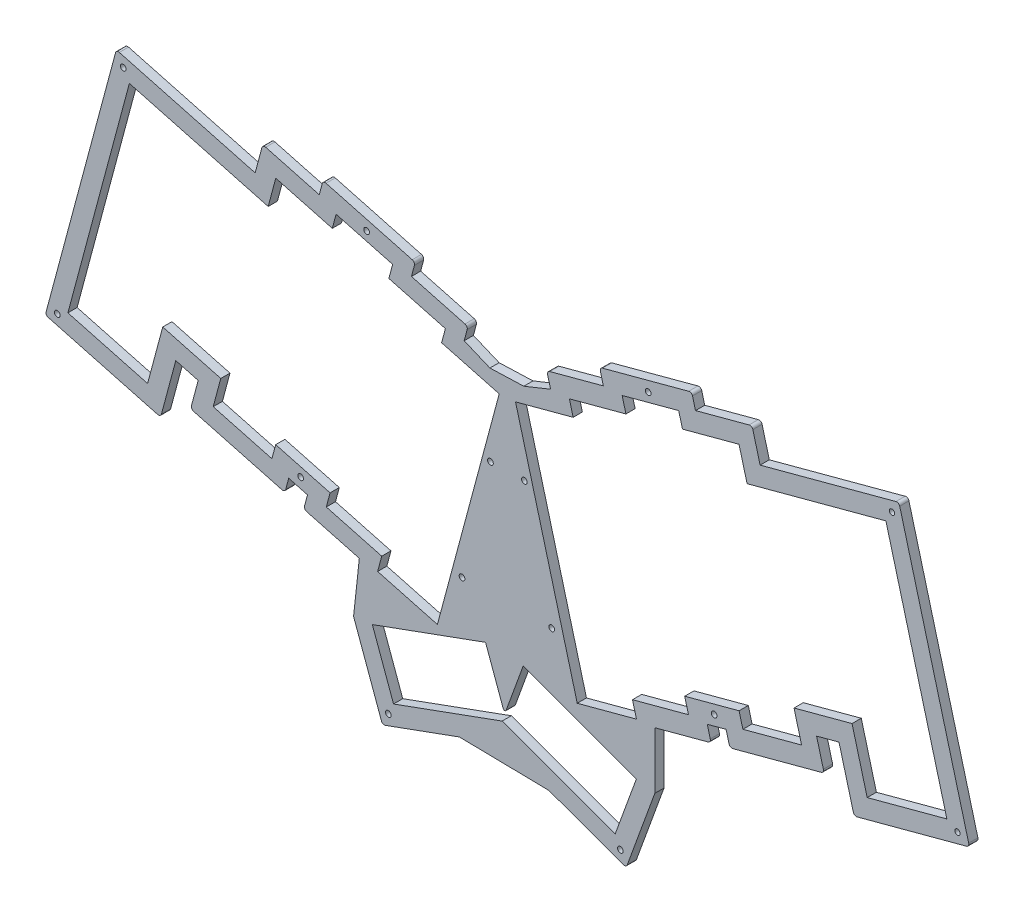
SolidWorks part; units mm, degrees
ref_plane "Front Plane" through (0, 0, 0) normal (0, 0, 1) x (1, 0, 0)
ref_plane "Top Plane" through (0, 0, 0) normal (0, 1, 0) x (1, 0, 0)
ref_plane "Right Plane" through (0, 0, 0) normal (1, 0, 0) x (0, 0, -1)
sketch "Model" plane through (0, 0, 0) normal (0, 0, 1) x (1, 0, 0)
  line L0 (282.165, 226.202) -> (288.4436, 227.8841) construction
  line L1 (267.373, 281.405) -> (273.6516, 283.0871) construction
  line L2 (195.392, 284.0785) -> (194.5766, 287.1211) construction
  line L3 (100.681, 283.685) -> (101.4961, 286.7277) construction
  line L4 (168.22, 168.742) -> (181.234, 164.006) construction
  line L5 (181.234, 164.006) -> (185.972, 177.021) construction
  line L6 (185.972, 177.021) -> (172.956, 181.758) construction
  line L7 (172.956, 181.758) -> (168.22, 168.742) construction
  line L8 (132.176, 184.752) -> (133.281, 181.717) construction
  line L9 (133.281, 181.717) -> (131.706, 181.144) construction
  line L10 (131.706, 181.144) -> (130.099, 185.56) construction
  line L11 (130.099, 185.56) -> (117.085, 180.823) construction
  line L12 (117.085, 180.823) -> (118.692, 176.407) construction
  line L13 (118.692, 176.407) -> (117.118, 175.834) construction
  line L14 (117.118, 175.834) -> (116.013, 178.869) construction
  line L15 (116.013, 178.869) -> (109.812, 176.612) construction
  line L16 (109.812, 176.612) -> (110.917, 173.576) construction
  line L17 (110.917, 173.576) -> (110.141, 173.294) construction
  line L18 (110.141, 173.294) -> (111.048, 170.804) construction
  line L19 (111.048, 170.804) -> (111.822, 171.086) construction
  line L20 (111.822, 171.086) -> (113.968, 165.194) construction
  line L21 (113.968, 165.194) -> (115.588, 165.784) construction
  line L22 (115.588, 165.784) -> (115.999, 164.656) construction
  line L23 (115.999, 164.656) -> (118.959, 165.734) construction
  line L24 (118.959, 165.734) -> (118.549, 166.861) construction
  line L25 (118.549, 166.861) -> (120.169, 167.452) construction
  line L26 (120.169, 167.452) -> (118.641, 171.651) construction
  line L27 (118.641, 171.651) -> (120.215, 172.224) construction
  line L28 (120.215, 172.224) -> (121.821, 167.809) construction
  line L29 (121.821, 167.809) -> (134.837, 172.545) construction
  line L30 (134.837, 172.545) -> (133.23, 176.962) construction
  line L31 (133.23, 176.962) -> (134.804, 177.535) construction
  line L32 (134.804, 177.535) -> (136.332, 173.335) construction
  line L33 (136.332, 173.335) -> (137.953, 173.925) construction
  line L34 (137.953, 173.925) -> (138.363, 172.796) construction
  line L35 (138.363, 172.796) -> (141.323, 173.874) construction
  line L36 (141.323, 173.874) -> (140.913, 175.001) construction
  line L37 (140.913, 175.001) -> (142.533, 175.592) construction
  line L38 (142.533, 175.592) -> (140.389, 181.483) construction
  line L39 (140.389, 181.483) -> (141.165, 181.766) construction
  line L40 (141.165, 181.766) -> (140.258, 184.256) construction
  line L41 (140.258, 184.256) -> (139.484, 183.974) construction
  line L42 (139.484, 183.974) -> (138.378, 187.009) construction
  line L43 (138.378, 187.009) -> (132.176, 184.752) construction
  line L44 (150.319, 175.258) -> (163.333, 170.521) construction
  line L45 (163.333, 170.521) -> (168.071, 183.535) construction
  line L46 (168.071, 183.535) -> (155.055, 188.273) construction
  line L47 (155.055, 188.273) -> (150.319, 175.258) construction
  line L48 (109.952, 197.835) -> (123.33, 194.251) construction
  line L49 (123.33, 194.251) -> (126.916, 207.629) construction
  line L50 (126.916, 207.629) -> (113.537, 211.213) construction
  line L51 (113.537, 211.213) -> (109.952, 197.835) construction
  line L52 (169.157, 208.022) -> (172.741, 194.644) construction
  line L53 (172.741, 194.644) -> (186.119, 198.228) construction
  line L54 (186.119, 198.228) -> (182.535, 211.607) construction
  line L55 (182.535, 211.607) -> (169.157, 208.022) construction
  line L56 (92.7848, 207.366) -> (106.163, 203.781) construction
  line L57 (106.163, 203.781) -> (109.747, 217.159) construction
  line L58 (109.747, 217.159) -> (96.369, 220.744) construction
  line L59 (96.369, 220.744) -> (92.7848, 207.366) construction
  line L60 (186.326, 217.552) -> (189.91, 204.174) construction
  line L61 (189.91, 204.174) -> (203.288, 207.759) construction
  line L62 (203.288, 207.759) -> (199.704, 221.137) construction
  line L63 (199.704, 221.137) -> (186.326, 217.552) construction
  line L64 (114.883, 216.236) -> (128.261, 212.652) construction
  line L65 (128.261, 212.652) -> (131.845, 226.03) construction
  line L66 (131.845, 226.03) -> (118.467, 229.614) construction
  line L67 (118.467, 229.614) -> (114.883, 216.236) construction
  line L68 (164.226, 226.423) -> (167.812, 213.045) construction
  line L69 (167.812, 213.045) -> (181.19, 216.629) construction
  line L70 (181.19, 216.629) -> (177.604, 230.007) construction
  line L71 (177.604, 230.007) -> (164.226, 226.423) construction
  line L72 (75.6158, 216.896) -> (88.9938, 213.312) construction
  line L73 (88.9938, 213.312) -> (92.5781, 226.69) construction
  line L74 (92.5781, 226.69) -> (79.2, 230.274) construction
  line L75 (79.2, 230.274) -> (75.6158, 216.896) construction
  line L76 (55.9827, 217.227) -> (69.3607, 213.643) construction
  line L77 (69.3607, 213.643) -> (72.9449, 227.021) construction
  line L78 (72.9449, 227.021) -> (59.5672, 230.605) construction
  line L79 (59.5672, 230.605) -> (55.9827, 217.227) construction
  line L80 (203.494, 227.083) -> (207.078, 213.705) construction
  line L81 (207.078, 213.705) -> (220.457, 217.29) construction
  line L82 (220.457, 217.29) -> (216.872, 230.668) construction
  line L83 (216.872, 230.668) -> (203.494, 227.083) construction
  line L84 (223.128, 227.414) -> (226.712, 214.036) construction
  line L85 (226.712, 214.036) -> (240.09, 217.62) construction
  line L86 (240.09, 217.62) -> (236.506, 230.998) construction
  line L87 (236.506, 230.998) -> (223.128, 227.414) construction
  line L88 (12.1157, 219.121) -> (25.4937, 215.536) construction
  line L89 (25.4937, 215.536) -> (29.078, 228.914) construction
  line L90 (29.078, 228.914) -> (15.7, 232.499) construction
  line L91 (15.7, 232.499) -> (12.1157, 219.121) construction
  line L92 (266.995, 229.307) -> (270.579, 215.929) construction
  line L93 (270.579, 215.929) -> (283.957, 219.513) construction
  line L94 (283.957, 219.513) -> (280.373, 232.891) construction
  line L95 (280.373, 232.891) -> (266.995, 229.307) construction
  line L96 (97.7138, 225.767) -> (111.092, 222.183) construction
  line L97 (111.092, 222.183) -> (114.677, 235.56) construction
  line L98 (114.677, 235.56) -> (101.299, 239.145) construction
  line L99 (101.299, 239.145) -> (97.7138, 225.767) construction
  line L100 (181.394, 235.953) -> (184.98, 222.575) construction
  line L101 (184.98, 222.575) -> (198.357, 226.159) construction
  line L102 (198.357, 226.159) -> (194.773, 239.538) construction
  line L103 (194.773, 239.538) -> (181.394, 235.953) construction
  line L104 (40.0473, 231.357) -> (53.425, 227.773) construction
  line L105 (53.425, 227.773) -> (57.0096, 241.151) construction
  line L106 (57.0096, 241.151) -> (43.6316, 244.735) construction
  line L107 (43.6316, 244.735) -> (40.0473, 231.357) construction
  line L108 (239.062, 241.545) -> (242.648, 228.166) construction
  line L109 (242.648, 228.166) -> (256.024, 231.75) construction
  line L110 (256.024, 231.75) -> (252.44, 245.128) construction
  line L111 (252.44, 245.128) -> (239.062, 241.545) construction
  line L112 (119.814, 234.637) -> (133.192, 231.053) construction
  line L113 (133.192, 231.053) -> (136.776, 244.431) construction
  line L114 (136.776, 244.431) -> (123.396, 248.015) construction
  line L115 (123.396, 248.015) -> (119.814, 234.637) construction
  line L116 (159.297, 244.824) -> (162.88, 231.445) construction
  line L117 (162.88, 231.445) -> (176.258, 235.03) construction
  line L118 (176.258, 235.03) -> (172.675, 248.408) construction
  line L119 (172.675, 248.408) -> (159.297, 244.824) construction
  line L120 (80.5462, 235.297) -> (93.9243, 231.713) construction
  line L121 (93.9243, 231.713) -> (97.5099, 245.091) construction
  line L122 (97.5099, 245.091) -> (84.1304, 248.675) construction
  line L123 (84.1304, 248.675) -> (80.5462, 235.297) construction
  line L124 (60.912, 235.628) -> (74.2901, 232.044) construction
  line L125 (74.2901, 232.044) -> (77.8757, 245.422) construction
  line L126 (77.8757, 245.422) -> (64.4977, 249.006) construction
  line L127 (64.4977, 249.006) -> (60.912, 235.628) construction
  line L128 (198.563, 245.484) -> (202.147, 232.106) construction
  line L129 (202.147, 232.106) -> (215.525, 235.692) construction
  line L130 (215.525, 235.692) -> (211.941, 249.069) construction
  line L131 (211.941, 249.069) -> (198.563, 245.484) construction
  line L132 (218.196, 245.814) -> (221.782, 232.436) construction
  line L133 (221.782, 232.436) -> (235.16, 236.021) construction
  line L134 (235.16, 236.021) -> (231.574, 249.399) construction
  line L135 (231.574, 249.399) -> (218.196, 245.814) construction
  line L136 (17.045, 237.521) -> (30.423, 233.937) construction
  line L137 (30.423, 233.937) -> (34.0086, 247.315) construction
  line L138 (34.0086, 247.315) -> (20.6306, 250.899) construction
  line L139 (20.6306, 250.899) -> (17.045, 237.521) construction
  line L140 (262.063, 247.708) -> (265.649, 234.33) construction
  line L141 (265.649, 234.33) -> (279.026, 237.914) construction
  line L142 (279.026, 237.914) -> (275.442, 251.292) construction
  line L143 (275.442, 251.292) -> (262.063, 247.708) construction
  line L144 (102.646, 244.168) -> (116.024, 240.584) construction
  line L145 (116.024, 240.584) -> (119.607, 253.962) construction
  line L146 (119.607, 253.962) -> (106.229, 257.546) construction
  line L147 (106.229, 257.546) -> (102.646, 244.168) construction
  line L148 (176.465, 254.354) -> (180.049, 240.976) construction
  line L149 (180.049, 240.976) -> (193.427, 244.56) construction
  line L150 (193.427, 244.56) -> (189.843, 257.938) construction
  line L151 (189.843, 257.938) -> (176.465, 254.354) construction
  line L152 (44.9778, 249.759) -> (58.3558, 246.174) construction
  line L153 (58.3558, 246.174) -> (61.94, 259.553) construction
  line L154 (61.94, 259.553) -> (48.562, 263.136) construction
  line L155 (48.562, 263.136) -> (44.9778, 249.759) construction
  line L156 (234.133, 259.945) -> (237.717, 246.567) construction
  line L157 (237.717, 246.567) -> (251.095, 250.151) construction
  line L158 (251.095, 250.151) -> (247.511, 263.529) construction
  line L159 (247.511, 263.529) -> (234.133, 259.945) construction
  line L160 (124.743, 253.038) -> (138.122, 249.454) construction
  line L161 (138.122, 249.454) -> (141.707, 262.832) construction
  line L162 (141.707, 262.832) -> (128.329, 266.416) construction
  line L163 (128.329, 266.416) -> (124.743, 253.038) construction
  line L164 (154.365, 263.224) -> (157.951, 249.845) construction
  line L165 (157.951, 249.845) -> (171.329, 253.432) construction
  line L166 (171.329, 253.432) -> (167.743, 266.809) construction
  line L167 (167.743, 266.809) -> (154.365, 263.224) construction
  line L168 (85.477, 253.699) -> (98.855, 250.114) construction
  line L169 (98.855, 250.114) -> (102.439, 263.492) construction
  line L170 (102.439, 263.492) -> (89.0612, 267.076) construction
  line L171 (89.0612, 267.076) -> (85.477, 253.699) construction
  line L172 (65.8442, 254.03) -> (79.2219, 250.443) construction
  line L173 (79.2219, 250.443) -> (82.8065, 263.823) construction
  line L174 (82.8065, 263.823) -> (69.427, 267.407) construction
  line L175 (69.427, 267.407) -> (65.8442, 254.03) construction
  line L176 (193.632, 263.885) -> (197.218, 250.507) construction
  line L177 (197.218, 250.507) -> (210.596, 254.092) construction
  line L178 (210.596, 254.092) -> (207.01, 267.47) construction
  line L179 (207.01, 267.47) -> (193.632, 263.885) construction
  line L180 (213.267, 264.215) -> (216.851, 250.837) construction
  line L181 (216.851, 250.837) -> (230.229, 254.422) construction
  line L182 (230.229, 254.422) -> (226.645, 267.8) construction
  line L183 (226.645, 267.8) -> (213.267, 264.215) construction
  line L184 (21.977, 255.922) -> (35.355, 252.338) construction
  line L185 (35.355, 252.338) -> (38.9378, 265.716) construction
  line L186 (38.9378, 265.716) -> (25.5598, 269.3) construction
  line L187 (25.5598, 269.3) -> (21.977, 255.922) construction
  line L188 (257.132, 266.109) -> (260.718, 252.729) construction
  line L189 (260.718, 252.729) -> (274.096, 256.315) construction
  line L190 (274.096, 256.315) -> (270.512, 269.693) construction
  line L191 (270.512, 269.693) -> (257.132, 266.109) construction
  line L192 (107.575, 262.569) -> (120.953, 258.984) construction
  line L193 (120.953, 258.984) -> (124.539, 272.362) construction
  line L194 (124.539, 272.362) -> (111.161, 275.947) construction
  line L195 (111.161, 275.947) -> (107.575, 262.569) construction
  line L196 (171.534, 272.755) -> (175.118, 259.377) construction
  line L197 (175.118, 259.377) -> (188.496, 262.961) construction
  line L198 (188.496, 262.961) -> (184.912, 276.339) construction
  line L199 (184.912, 276.339) -> (171.534, 272.755) construction
  line L200 (49.9071, 268.159) -> (63.2852, 264.575) construction
  line L201 (63.2852, 264.575) -> (66.8708, 277.953) construction
  line L202 (66.8708, 277.953) -> (53.4928, 281.537) construction
  line L203 (53.4928, 281.537) -> (49.9071, 268.159) construction
  line L204 (229.201, 278.346) -> (232.786, 264.968) construction
  line L205 (232.786, 264.968) -> (246.164, 268.554) construction
  line L206 (246.164, 268.554) -> (242.579, 281.932) construction
  line L207 (242.579, 281.932) -> (229.201, 278.346) construction
  line L208 (90.4074, 272.099) -> (103.785, 268.515) construction
  line L209 (103.785, 268.515) -> (107.37, 281.893) construction
  line L210 (107.37, 281.893) -> (93.992, 285.477) construction
  line L211 (93.992, 285.477) -> (90.4074, 272.099) construction
  line L212 (70.7732, 272.43) -> (84.1513, 268.844) construction
  line L213 (84.1513, 268.844) -> (87.7369, 282.222) construction
  line L214 (87.7369, 282.222) -> (74.3589, 285.808) construction
  line L215 (74.3589, 285.808) -> (70.7732, 272.43) construction
  line L216 (188.703, 282.286) -> (192.286, 268.908) construction
  line L217 (192.286, 268.908) -> (205.664, 272.493) construction
  line L218 (205.664, 272.493) -> (202.081, 285.871) construction
  line L219 (202.081, 285.871) -> (188.703, 282.286) construction
  line L220 (208.336, 282.616) -> (211.92, 269.238) construction
  line L221 (211.92, 269.238) -> (225.298, 272.822) construction
  line L222 (225.298, 272.822) -> (221.714, 286.2) construction
  line L223 (221.714, 286.2) -> (208.336, 282.616) construction
  line L224 (26.9062, 274.323) -> (40.284, 270.739) construction
  line L225 (40.284, 270.739) -> (43.8697, 284.117) construction
  line L226 (43.8697, 284.117) -> (30.4919, 287.701) construction
  line L227 (30.4919, 287.701) -> (26.9062, 274.323) construction
  line L228 (252.203, 284.508) -> (255.786, 271.131) construction
  line L229 (255.786, 271.131) -> (269.165, 274.716) construction
  line L230 (269.165, 274.716) -> (265.581, 288.094) construction
  line L231 (265.581, 288.094) -> (252.203, 284.508) construction
  line L232 (37.1808, 285.909) -> (37.996, 288.9517) construction
  line L233 (28.6991, 281.012) -> (22.4207, 282.6948) construction
  line L234 (18.8047, 217.3285) -> (17.9893, 214.2859) construction
  line L235 (13.9078, 225.81) -> (7.6293, 227.4922) construction
  line L236 (277.268, 217.721) -> (278.0831, 214.6783) construction
  line L237 (271.2035, 292.2232) -> (291.0512, 218.1525)
  line L238 (241.3027, 224.5444) -> (243.7675, 215.3441)
  line L239 (81.0479, 284.015) -> (81.8635, 287.0576) construction
  line L240 (181.234, 164.006) -> (184.194, 162.9285) construction
  line L241 (91.0631, 284.5916) -> (72.6639, 289.5236)
  line L242 (117.85, 274.1545) -> (118.6654, 277.1971) construction
  line L243 (135.018, 264.624) -> (135.8331, 267.6667) construction
  line L244 (161.054, 265.0165) -> (160.2386, 268.0591) construction
  line L245 (178.223, 274.547) -> (177.4079, 277.5897) construction
  line L246 (215.025, 284.408) -> (214.2099, 287.4507) construction
  line L247 (258.892, 286.301) -> (258.2357, 288.7493) construction
  line L248 (196.599, 205.9665) -> (197.4144, 202.9239) construction
  line L249 (92.2965, 289.1937) -> (110.6958, 284.2617)
  line L250 (213.7675, 215.4975) -> (214.5828, 212.4548) construction
  line L251 (233.401, 215.828) -> (234.2161, 212.7853) construction
  line L252 (62.6717, 215.435) -> (61.8566, 212.3923) construction
  line L253 (82.3048, 215.104) -> (81.4897, 212.0613) construction
  line L254 (99.4739, 205.5735) -> (98.6586, 202.5309) construction
  line L255 (35.8867, 229.2106) -> (54.7701, 224.1516)
  line L256 (60.1818, 279.745) -> (60.9969, 282.7877) construction
  line L257 (72.6639, 289.5236) -> (70.1982, 280.3232)
  line L258 (105.8147, 195.273) -> (104.0964, 179.4507) construction
  line L259 (52.3052, 214.9511) -> (54.7701, 224.1516)
  line L260 (260.1862, 229.6041) -> (265.1156, 211.2042)
  line L261 (203.777, 289.5866) -> (185.3762, 284.6556)
  line L262 (30.9571, 210.8115) -> (35.8867, 229.2106)
  line L263 (141.707, 262.832) -> (142.5224, 265.8746) construction
  line L264 (154.365, 263.224) -> (153.5495, 266.2666) construction
  line L265 (181.234, 164.006) -> (180.1565, 161.046) construction
  line L266 (92.2965, 289.1937) -> (91.0631, 284.5916)
  line L267 (169.4396, 270.5248) -> (150.6904, 265.5004)
  line L268 (110.6958, 284.2617) -> (109.4634, 279.6637)
  line L269 (127.8626, 274.7318) -> (126.6303, 270.1341)
  line L270 (127.8626, 274.7318) -> (109.4634, 279.6637)
  line L271 (260.1862, 229.6041) -> (241.3027, 224.5444)
  line L272 (126.6303, 270.1341) -> (145.3813, 265.1084)
  line L273 (185.3762, 284.6556) -> (186.6084, 280.0546)
  line L274 (142.3447, 270.8715) -> (153.3719, 271.2634)
  line L275 (203.777, 289.5866) -> (205.0099, 284.986)
  line L276 (168.2073, 275.1248) -> (169.4396, 270.5248)
  line L277 (205.0099, 284.986) -> (223.4098, 289.9154)
  line L278 (223.4098, 289.9154) -> (226.0333, 280.1226)
  line L279 (186.6084, 280.0546) -> (168.2073, 275.1248)
  line L280 (104.0964, 179.4507) -> (110.9864, 160.5147)
  line L281 (152.687, 181.7655) -> (183.603, 170.5135) construction
  line L282 (110.5015, 171.0598) -> (141.4185, 182.3092) construction
  line L283 (27.2858, 222.225) -> (33.5644, 220.5428) construction
  line L284 (90.3394, 209.6904) -> (72.6399, 214.4322)
  line L285 (71.4079, 209.8335) -> (72.6399, 214.4322)
  line L286 (89.1069, 205.0898) -> (90.3394, 209.6904)
  line L287 (89.1069, 205.0898) -> (107.1497, 200.256)
  line L288 (107.1497, 200.256) -> (105.8147, 195.273)
  line L289 (110.9864, 160.5147) -> (131.4289, 167.9529)
  line L290 (71.4079, 209.8335) -> (52.3052, 214.9511)
  line L291 (5.0216, 217.7602) -> (25.0282, 292.4264)
  line L292 (130.099, 185.56) -> (121.821, 167.809) construction
  line L293 (190.0384, 195.7708) -> (190.0096, 178.9037) construction
  line L294 (235.89, 280.139) -> (235.2337, 282.5873) construction
  line L295 (162.6744, 167.408) -> (183.1165, 159.9688)
  line L296 (131.4289, 167.9529) -> (162.6744, 167.408) construction
  line L297 (5.0216, 217.7602) -> (30.9571, 210.8115)
  line L298 (46.7361, 229.565) -> (45.921, 226.5223) construction
  line L299 (265.1156, 211.2042) -> (291.0512, 218.1525)
  line L300 (25.0282, 292.4264) -> (70.1982, 280.3232)
  line L301 (226.0333, 280.1226) -> (271.2035, 292.2232)
  line L302 (216.1359, 206.6593) -> (215.3122, 209.7329) construction
  line L303 (128.329, 170.177) -> (129.4061, 167.2169) construction
  line L304 (249.336, 229.958) -> (250.1513, 226.9153) construction
  line L305 (268.787, 222.618) -> (262.5084, 220.9359) construction
  line L306 (109.952, 197.835) -> (106.7322, 198.6976) construction
  line L307 (-2.3268, 213.5174) -> (20.7855, 299.7748)
  line L308 (186.119, 198.228) -> (189.1617, 199.0431) construction
  line L309 (206.9661, 205.4835) -> (188.7445, 200.6005)
  line L310 (188.7445, 200.6005) -> (190.0384, 195.7708)
  line L311 (20.7855, 299.7748) -> (65.9558, 287.6716)
  line L312 (68.4216, 296.8725) -> (65.9558, 287.6716)
  line L313 (86.821, 291.9405) -> (68.4216, 296.8725)
  line L314 (88.0544, 296.5426) -> (86.821, 291.9405)
  line L315 (88.0544, 296.5426) -> (118.0445, 288.5037)
  line L316 (118.0445, 288.5037) -> (116.8121, 283.9057)
  line L317 (135.2113, 278.9738) -> (116.8121, 283.9057)
  line L318 (135.2113, 278.9738) -> (133.9791, 274.3762)
  line L319 (133.9791, 274.3762) -> (142.3447, 270.8715)
  line L320 (153.3719, 271.2634) -> (162.0915, 274.7674)
  line L321 (20.7855, 299.7748) -> (25.0282, 292.4264) construction
  line L322 (160.859, 279.3678) -> (162.0915, 274.7674)
  line L323 (179.2607, 284.2977) -> (160.859, 279.3678)
  line L324 (178.0286, 288.8984) -> (179.2607, 284.2977)
  line L325 (208.0195, 296.9352) -> (178.0286, 288.8984)
  line L326 (208.0195, 296.9352) -> (209.2525, 292.3342)
  line L327 (209.2525, 292.3342) -> (227.6528, 297.2637)
  line L328 (227.6528, 297.2637) -> (230.2763, 287.4708)
  line L329 (230.2763, 287.4708) -> (275.4462, 299.5713)
  line L330 (298.3998, 213.9096) -> (294.5027, 216.1597) construction
  line L331 (275.4462, 299.5713) -> (298.3998, 213.9096)
  line L332 (260.8726, 203.856) -> (298.3998, 213.9096)
  line L333 (255.9433, 222.2556) -> (260.8726, 203.856)
  line L334 (255.9433, 222.2556) -> (248.6509, 220.3017)
  line L335 (183.1165, 159.9688) -> (190.0096, 178.9037)
  line L336 (248.6509, 220.3017) -> (251.1158, 211.1012)
  line L337 (220.4222, 202.8783) -> (251.1158, 211.1012)
  line L338 (219.1898, 207.4775) -> (220.4222, 202.8783)
  line L339 (213.082, 205.8412) -> (219.1898, 207.4775)
  line L340 (206.9661, 205.4835) -> (205.7333, 210.084)
  line L341 (223.4323, 214.8256) -> (224.6648, 210.2265)
  line L342 (205.7333, 210.084) -> (223.4323, 214.8256)
  line L343 (214.3147, 201.2411) -> (213.082, 205.8412)
  line L344 (214.3147, 201.2411) -> (196.0393, 196.3437)
  line L345 (224.6648, 210.2265) -> (243.7675, 215.3441)
  line L346 (196.0393, 196.3437) -> (196.0078, 177.8406)
  line L347 (150.6904, 265.5004) -> (170.7656, 190.6076)
  line L348 (186.7023, 152.2789) -> (196.0078, 177.8406)
  line L349 (161.566, 161.4264) -> (186.7023, 152.2789)
  line L350 (132.4358, 161.9344) -> (161.566, 161.4264)
  line L351 (107.3996, 152.8248) -> (132.4358, 161.9344)
  line L352 (97.9807, 178.7109) -> (107.3996, 152.8248)
  line L353 (99.8582, 195.9979) -> (97.9807, 178.7109)
  line L354 (141.707, 262.832) -> (154.365, 263.224) construction
  line L355 (81.7586, 200.8468) -> (99.8582, 195.9979)
  line L356 (81.7586, 200.8468) -> (82.9911, 205.4475)
  line L357 (82.9911, 205.4475) -> (76.8829, 207.0839)
  line L358 (75.6509, 202.4852) -> (76.8829, 207.0839)
  line L359 (75.6509, 202.4852) -> (44.9569, 210.7082)
  line L360 (44.9569, 210.7082) -> (47.4218, 219.9086)
  line L361 (40.1295, 221.8623) -> (47.4218, 219.9086)
  line L362 (35.1999, 203.4631) -> (40.1295, 221.8623)
  line L363 (-2.3268, 213.5174) -> (35.1999, 203.4631)
  line L364 (20.7855, 299.7748) -> (23.0356, 295.8777) construction
  line L365 (142.5224, 265.8746) -> (153.5495, 266.2666) construction
  line L366 (275.4462, 299.5713) -> (271.2035, 292.2232) construction
  line L367 (291.0512, 218.1525) -> (298.3998, 213.9096) construction
  line L368 (-2.3268, 213.5174) -> (5.0216, 217.7602) construction
  line L369 (107.3996, 152.8248) -> (110.9864, 160.5147) construction
  line L370 (183.1165, 159.9688) -> (186.7023, 152.2789) construction
  line L371 (107.3996, 152.8248) -> (109.3018, 156.903) construction
  line L372 (184.8006, 156.3573) -> (186.7023, 152.2789) construction
  line L373 (106.163, 203.781) -> (189.91, 204.174) construction
  line L374 (101.4961, 286.7277) -> (103.0495, 292.5232) construction
  line L375 (194.5766, 287.1211) -> (193.0241, 292.9168) construction
  line L376 (23.0356, 295.8777) -> (23.8591, 298.9513) construction
  line L377 (193.0241, 292.9168) -> (193.8474, 289.8432) construction
  line L378 (214.5828, 212.4548) -> (216.1359, 206.6593) construction
  line L379 (103.0495, 292.5232) -> (102.2257, 289.4497) construction
  line L380 (275.4462, 299.5713) -> (273.1961, 295.6743) construction
  line L381 (-2.3268, 213.5174) -> (1.5702, 215.7675) construction
  line L382 (81.4897, 212.0613) -> (79.937, 206.2657) construction
  line L383 (81.4897, 212.0613) -> (79.937, 206.2657) construction
  line L384 (214.5828, 212.4548) -> (216.1359, 206.6593) construction
  line L385 (145.3813, 265.1084) -> (125.265, 190.0622)
  line L386 (190.0384, 195.7708) -> (170.7656, 190.6076)
  line L387 (148.0359, 266.0706) -> (148.0365, 203.9775) construction
  line L388 (105.8147, 195.273) -> (125.265, 190.0622)
  line L389 (104.0964, 179.4507) -> (140.9309, 192.8582)
  line L390 (190.0096, 178.9037) -> (153.1726, 192.3111)
  line L391 (152.687, 181.7655) -> (149.727, 182.8428) construction
  line L392 (131.4289, 167.9529) -> (146.3042, 173.3654)
  line L393 (153.1726, 192.3111) -> (147.152, 175.767)
  line L394 (146.3042, 173.3654) -> (162.6744, 167.408)
  line L395 (141.4185, 182.3092) -> (144.3786, 183.3863) construction
  line L396 (147.152, 175.767) -> (140.9309, 192.8582)
  line L397 (110.5015, 171.0598) -> (107.5414, 169.9827) construction
  line L398 (123.592, 183.1915) -> (122.5136, 186.1545) construction
  line L399 (105.8147, 195.273) -> (183.187, 229.264) construction
  line L400 (171.073, 185.7954) -> (164.1828, 166.8591) construction
  line L401 (112.8845, 228.8715) -> (190.0384, 195.7708) construction
  line L402 (105.8147, 195.273) -> (133.2811, 207.3395) construction
  line L403 (162.4685, 207.5989) -> (190.0384, 195.7708) construction
  line L404 (136.776, 244.431) -> (159.297, 244.824) construction
  line L405 (136.776, 244.431) -> (142.5224, 244.5313) construction
  line L406 (159.297, 244.824) -> (153.5495, 244.7237) construction
  line L407 (79.937, 206.2657) -> (80.7604, 209.3393) construction
  line L425 (164.1828, 166.8591) -> (183.1165, 159.9688) construction
  line L426 (190.0096, 178.9037) -> (171.073, 185.7954) construction
  line L427 (99.8582, 195.9979) -> (99.8582, 195.9979) construction
  line L428 (99.8582, 195.9979) -> (97.9807, 178.7109) construction
  line L429 (150.6904, 265.5004) -> (145.3813, 265.1084) construction
  line L430 (149.6841, 271.4425) -> (145.9529, 271.1669) construction
  line L431 (133.9791, 274.3762) -> (145.9529, 271.1669) construction
  line L432 (162.0915, 274.7674) -> (149.6841, 271.4425) construction
  line L433 (256.6831, 294.5449) -> (275.4462, 299.5713) construction
  line L434 (230.2763, 287.4708) -> (256.6831, 294.5449) construction
  line L435 (196.0393, 196.3437) -> (196.0393, 196.3437) construction
  line L436 (196.0393, 196.3437) -> (196.0078, 177.8406) construction
  line L437 (226.0333, 280.1226) -> (258.2357, 288.7493) construction
  line L438 (258.2357, 288.7493) -> (271.2035, 292.2232) construction
  circle A0 centre (23.0356, 295.8777) radius 0.925
  circle A1 centre (109.3018, 156.903) radius 0.925
  circle A2 centre (184.8006, 156.3573) radius 0.925
  circle A3 centre (193.8474, 289.8432) radius 0.925
  circle A4 centre (102.2257, 289.4497) radius 0.925
  circle A5 centre (273.1961, 295.6743) radius 0.875
  circle A6 centre (1.5702, 215.7675) radius 0.925
  circle A7 centre (294.5027, 216.1597) radius 0.875
  circle A8 centre (80.7604, 209.3393) radius 0.925
  circle A9 centre (215.3122, 209.7329) radius 0.925
  circle A10 centre (133.2811, 207.3395) radius 0.925
  circle A11 centre (162.4685, 207.5989) radius 0.925
  circle A12 centre (142.5224, 244.5313) radius 0.925
  circle A13 centre (153.5495, 244.7237) radius 0.925
  point P253 (61.8566, 212.3923)
  point P289 (81.8635, 287.0576)
  point P293 (194.5766, 287.1211)
  point P295 (101.4961, 286.7277)
  point P297 (81.4897, 212.0613)
  point P361 (125.96, 176.6845)
  point P362 (125.96, 176.6845)
  point P374 (214.5828, 212.4548)
  point P377 (234.2161, 212.7853)
  point P378 (177.4079, 277.5897)
  point P386 (214.2099, 287.4507)
  dimension "D5" = 6
  dimension "D4" = 1.85
  dimension "D7" = 30.011
  dimension "D8" = 30
  dimension "D9" = 1.75
  dimension "D1" = 9.5249
  dimension "D2" = 6.5
  dimension "D3" = 5
  dimension "D6" = 4.5
  dimension "D10" = 4.5
extrude "Boss-Extrude1" add sketch "Model" against normal blind 3
fillet "Fillet2" radius 0.5 1 edges at (147.152, 175.767, -1.5)
fillet "Fillet3" radius 1 22 edges at (20.7855, 299.7748, -1.5) (68.4216, 296.8725, -1.5) (88.0544, 296.5426, -1.5) (135.2113, 278.9738, -1.5) (160.859, 279.3678, -1.5) (178.0286, 288.8984, -1.5) (208.0195, 296.9352, -1.5) (227.6528, 297.2637, -1.5) (275.4462, 299.5713, -1.5) (298.3998, 213.9096, -1.5) (260.8726, 203.856, -1.5) (251.1158, 211.1012, -1.5) (220.4222, 202.8783, -1.5) (214.3147, 201.2411, -1.5) (186.7023, 152.2789, -1.5) (107.3996, 152.8248, -1.5) (81.7586, 200.8468, -1.5) (75.6509, 202.4852, -1.5) (44.9569, 210.7082, -1.5) (35.1999, 203.4631, -1.5) (-2.3268, 213.5174, -1.5) (118.0445, 288.5037, -1.5)
